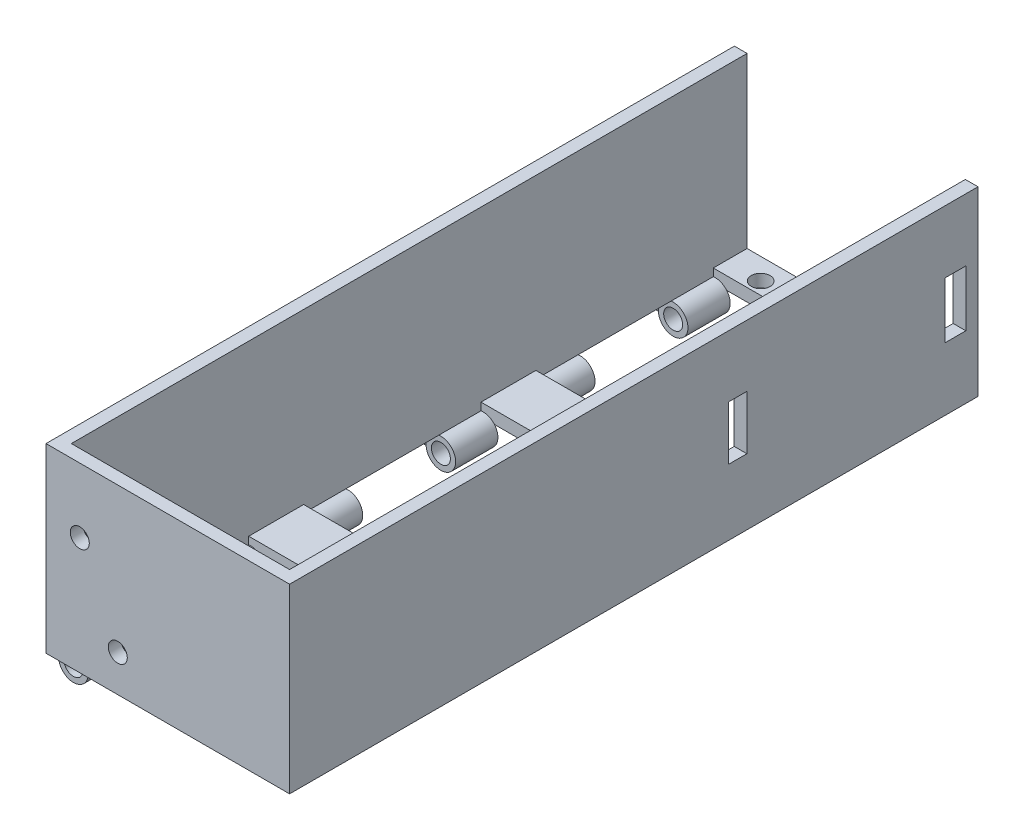
SolidWorks part; units mm, degrees
ref_plane "Front Plane" through (0, 0, 0) normal (0, 0, 1) x (1, 0, 0)
ref_plane "Top Plane" through (0, 0, 0) normal (0, 1, 0) x (1, 0, 0)
ref_plane "Right Plane" through (0, 0, 0) normal (1, 0, 0) x (0, 0, -1)
sketch "Sketch1" plane through (0, 0, 0) normal (0, 0, 1) x (1, 0, 0)
  line L0 (0, 0) -> (0, -10)
  line L1 (0, -10) -> (0, -40)
  line L2 (0, -40) -> (51.6786, -40)
  line L5 (-3, 0) -> (-3, -10)
  line L6 (-3, -10) -> (-3, -43)
  line L7 (-3, -43) -> (54.6786, -43)
  line L10 (-3, 0) -> (0, 0)
  line L12 (51.6786, -40) -> (51.6786, 0)
  line L13 (51.6786, -40) -> (51.6786, 37.6119) construction
  line L14 (51.6786, 37.6119) -> (67.0297, -2.1736) construction
  line L15 (54.6786, -43) -> (54.6786, 21.503) construction
  line L16 (54.6786, 21.503) -> (64.2308, -3.2535) construction
  line L17 (51.6786, 0) -> (54.6786, 0)
  line L18 (54.6786, 0) -> (54.6786, -43)
  dimension "D2" = 10
  dimension "D3" = 30
  dimension "D5" = 3
  dimension "D1" = 3
extrude "Boss-Extrude1" add sketch "Sketch1" along normal blind 160
sketch "Sketch2" plane through (0, 0, 0) normal (0, 1, 0) x (1, 0, 0)
  line L0 (51.6786, -160) -> (0, -160) construction
  line L1 (49, -8) -> (0, -8)
  line L2 (49, -8) -> (49, -50)
  line L3 (49, -50) -> (0, -50)
  line L4 (0, -8) -> (0, -50)
  line L5 (49, -63) -> (0, -63)
  line L6 (49, -63) -> (49, -105)
  line L7 (49, -105) -> (0, -105)
  line L8 (0, -63) -> (0, -105)
  line L9 (49, -118) -> (0, -118)
  line L10 (49, -118) -> (49, -160)
  line L11 (49, -160) -> (0, -160)
  line L12 (0, -118) -> (0, -160)
  line L13 (0, -160) -> (0, 0) construction
  dimension "D1" = 42
  dimension "D2" = 13
  dimension "D3" = 42
  dimension "D4" = 13
  dimension "D5" = 42
  dimension "D6" = 49
extrude "Cut-Extrude1" cut sketch "Sketch2" against normal through all
sketch "Sketch3" plane through (0, 0, 160) normal (0, 0, 1) x (1, 0, 0)
  line L0 (-3, 0) -> (54.6786, 0)
  line L1 (54.6786, 0) -> (54.6786, -43)
  line L2 (54.6786, -43) -> (0, -43)
  line L10 (0, 0) -> (-3, 0)
  line L11 (-3, 0) -> (-3, -43)
  line L13 (-3, -43) -> (0, -43)
  line L18 (0, -43) -> (0, 0)
  line L21 (-3, 0) -> (-3, -43)
  line L23 (-3, -43) -> (0, -43)
  dimension "D1" = 0
extrude "Boss-Extrude2" add sketch "Sketch3" along normal blind 3
sketch "Sketch4" plane through (0, 0, 163) normal (0, 0, 1) x (1, 0, 0)
  circle A0 centre (14, -34.2995) radius 2.25 construction
  circle A1 centre (5, -15.3106) radius 2.25 construction
  circle A2 centre (14, -34.2995) radius 2.25
  circle A3 centre (5, -15.3106) radius 2.25
extrude "Cut-Extrude2" cut sketch "Sketch4" against normal up to next
sketch "Sketch5" plane through (0, -40, 0) normal (0, 1, 0) x (1, 0, 0)
  line L14 (49, -8) -> (49, -50)
  line L15 (49, -50) -> (0, -50)
  line L16 (0, -50) -> (0, -63)
  line L17 (0, -63) -> (49, -63)
  line L18 (49, -63) -> (49, -105)
  line L19 (49, -105) -> (0, -105)
  line L20 (0, -105) -> (0, -118)
  line L21 (0, -118) -> (49, -118)
  line L22 (49, -118) -> (49, -160)
  line L23 (49, -160) -> (51.6786, -160)
  line L24 (51.6786, -160) -> (51.6786, 0)
  line L25 (51.6786, 0) -> (0, 0)
  line L26 (0, 0) -> (0, -8)
  line L27 (0, -8) -> (49, -8)
  line L28 (49, -8) -> (49, -50)
  line L29 (49, -50) -> (0, -50)
  line L30 (0, -50) -> (0, -63)
  line L31 (0, -63) -> (49, -63)
  line L32 (49, -63) -> (49, -105)
  line L33 (49, -105) -> (0, -105)
  line L34 (0, -105) -> (0, -118)
  line L35 (0, -118) -> (49, -118)
  line L36 (49, -118) -> (49, -160)
  line L37 (49, -160) -> (51.6786, -160)
  line L38 (51.6786, -160) -> (51.6786, 0)
  line L39 (51.6786, 0) -> (0, 0)
  line L40 (0, 0) -> (0, -8)
  line L41 (0, -8) -> (49, -8)
  ellipse E0 centre (8.2809, -5.054) end of major axis (6.0309, -5.054) minor radius 2.2278 construction
  ellipse E1 centre (8.2809, -5.054) end of major axis (6.0309, -5.054) minor radius 2.2278
  dimension "D1" = 0
extrude "Cut-Extrude3" cut sketch "Sketch5" against normal up to next contours E1 region at (8.2809, -40, 5.054)
sketch "Sketch6" plane through (0, 0, 160) normal (0, 0, 1) x (1, 0, 0)
  line L0 (-3, 0) -> (-3, -43) construction
  line L4 (6.0309, -43) -> (10.5309, -43) construction
  circle A0 centre (0.5, -45.25) radius 2.25
  circle A1 centre (0.5, -45.25) radius 3.5
  dimension "D1" = 7
  dimension "D2" = 4.5
extrude "Boss-Extrude3" add sketch "Sketch6" against normal blind 10
pattern_linear "LPattern1" count 3 spacing 55 along (0, 0, -1) of "Boss-Extrude3"
sketch "Sketch8" plane through (0, 0, 118) normal (0, 0, 1) x (1, 0, 0)
  circle A0 centre (0.5, -45.25) radius 2.25 construction
  arc A1 (-2.181, -43) -> (0, -41.7859) centre (0.5, -45.25) ccw construction
  circle A2 centre (0.5, -45.25) radius 2.25
  circle A3 centre (0.5, -45.25) radius 3.5
extrude "Boss-Extrude5" add sketch "Sketch8" along normal blind 10
pattern_linear "LPattern4" count 3 spacing 55 along (0, 0, -1) of "Boss-Extrude5"
sketch "Sketch9" plane through (0, -43, 0) normal (0, -1, 0) x (1, 0, 0)
  line L0 (-3, 163) -> (-3, 0) construction
  line L1 (-2.181, 160) -> (-3, 160)
  line L2 (-2.181, 160) -> (-2.181, 150)
  line L3 (-2.181, 150) -> (-3, 150)
  line L4 (-3, 160) -> (-3, 150)
  line L5 (-3, 150) -> (4, 150) construction
  line L6 (-3, 118) -> (4, 118) construction
  line L7 (-2.181, 105) -> (-3, 105)
  line L8 (-2.181, 105) -> (-2.181, 95)
  line L9 (-2.181, 95) -> (-3, 95)
  line L10 (-3, 105) -> (-3, 95)
  line L11 (-2.181, 128) -> (-3, 128)
  line L12 (-2.181, 128) -> (-2.181, 118)
  line L13 (-2.181, 118) -> (-3, 118)
  line L14 (-3, 128) -> (-3, 118)
  line L15 (-2.181, 73) -> (-3, 73)
  line L16 (-2.181, 73) -> (-2.181, 63)
  line L17 (-2.181, 63) -> (-3, 63)
  line L18 (-3, 73) -> (-3, 63)
  line L19 (-2.181, 50) -> (-3, 50)
  line L20 (-2.181, 50) -> (-2.181, 40)
  line L21 (-2.181, 40) -> (-3, 40)
  line L22 (-3, 50) -> (-3, 40)
  line L23 (-2.181, 18) -> (-3, 18)
  line L24 (-2.181, 18) -> (-2.181, 8)
  line L25 (-2.181, 8) -> (-3, 8)
  line L26 (-3, 18) -> (-3, 8)
  line L27 (-3, 95) -> (4, 95) construction
  line L28 (-3, 63) -> (4, 63) construction
  line L29 (-3, 40) -> (4, 40) construction
extrude "Boss-Extrude6" add sketch "Sketch9" along normal up to next
sketch "Sketch10" plane through (-3, 0, 0) normal (-1, 0, 0) x (0, 0, 1)
  line L0 (128, -45.25) -> (128, -43) construction
  line L1 (122.4, -43) -> (125.4, -43)
  line L2 (122.4, -43) -> (122.4, -48)
  line L3 (122.4, -48) -> (125.4, -48)
  line L4 (125.4, -43) -> (125.4, -48)
  line L5 (122.4, -15.4) -> (125.4, -15.4)
  line L6 (122.4, -15.4) -> (122.4, -20.4)
  line L7 (122.4, -20.4) -> (125.4, -20.4)
  line L8 (125.4, -15.4) -> (125.4, -20.4)
  line L9 (150, -43) -> (128, -43) construction
  dimension "D1" = 2.6
  dimension "D2" = 22.6
  dimension "D3" = 5
  dimension "D4" = 5
  dimension "D5" = 3
  dimension "D6" = 3
extrude "Boss-Extrude7" add sketch "Sketch10" along normal blind 13
pattern_linear "LPattern5" count 3 spacing 55 along (0, 0, -1) of "Boss-Extrude7"
sketch "Sketch11" plane through (0, 0, 125.4) normal (0, 0, 1) x (1, 0, 0)
  circle A0 centre (-9.2, -45.95) radius 1
  circle A1 centre (-9.2, -17.45) radius 1
  dimension "D1" = 2
extrude "Cut-Extrude4" cut sketch "Sketch11" against normal through all
fillet "Fillet1" radius 4 9 edges at (-3, -15.4, 123.9) (-3, -17.9, 122.4) (-3, -44.125, 122.4) (-3, -44.125, 12.4) (-3, -17.9, 12.4) (-3, -15.4, 13.9) (-3, -44.125, 67.4) (-3, -15.4, 68.9) (-3, -17.9, 67.4)
sketch "Sketch12" plane through (0, -40, 0) normal (0, 1, 0) x (1, 0, 0)
  line L1 (32.6182, -9.1719) -> (19.1667, -9.1719)
  line L2 (32.6182, -9.1719) -> (32.6182, -2.8815)
  line L3 (32.6182, -2.8815) -> (19.1667, -2.8815)
  line L4 (19.1667, -9.1719) -> (19.1667, -2.8815)
  line L5 (31.0636, -58.1853) -> (19.4684, -58.1853)
  line L6 (31.0636, -58.1853) -> (31.0636, -53.5298)
  line L7 (31.0636, -53.5298) -> (19.4684, -53.5298)
  line L8 (19.4684, -58.1853) -> (19.4684, -53.5298)
extrude "Cut-Extrude5" cut sketch "Sketch12" against normal through all
sketch "Sketch13" plane through (51.6786, 0, 0) normal (-1, 0, 0) x (0, 0, 1)
  line L1 (2.879, -14.7915) -> (7.8356, -14.7915)
  line L2 (2.879, -14.7915) -> (2.879, -28.0944)
  line L3 (2.879, -28.0944) -> (7.8356, -28.0944)
  line L4 (7.8356, -14.7915) -> (7.8356, -28.0944)
  line L5 (54.7205, -14.5899) -> (59.0899, -14.5899)
  line L6 (54.7205, -14.5899) -> (54.7205, -27.3851)
  line L7 (54.7205, -27.3851) -> (59.0899, -27.3851)
  line L8 (59.0899, -14.5899) -> (59.0899, -27.3851)
  line L9 (50.9179, -252.7121) -> (57.0548, -252.7121)
  line L10 (50.9179, -252.7121) -> (50.9179, -267.8576)
  line L11 (50.9179, -267.8576) -> (57.0548, -267.8576)
  line L12 (57.0548, -252.7121) -> (57.0548, -267.8576)
extrude "Cut-Extrude8" cut sketch "Sketch13" against normal through all
sketch "Sketch14" plane through (0, 0, 150) normal (0, 0, -1) x (-1, 0, 0)
  circle A0 centre (-0.5, -45.25) radius 3.5
extrude "Cut-Extrude9" cut sketch "Sketch14" along normal blind 22
pattern_linear "LPattern6" count 3 spacing 55 along (0, 0, -1) of "Cut-Extrude9"
